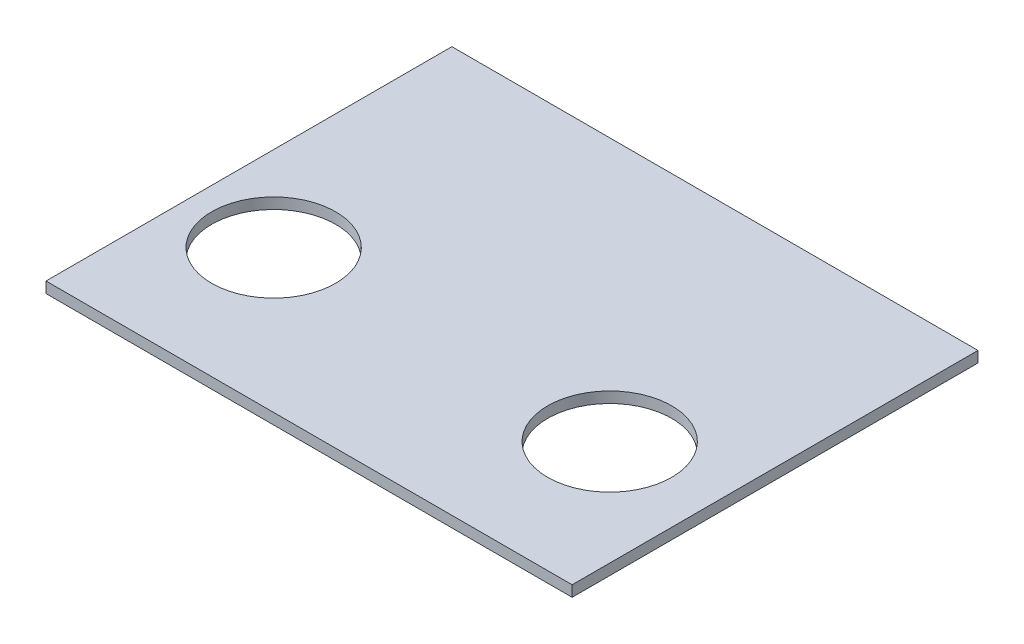
SolidWorks part; units mm, degrees
ref_plane "Plan de face" through (0, 0, 0) normal (0, 0, 1) x (1, 0, 0)
ref_plane "Plan de dessus" through (0, 0, 0) normal (0, 1, 0) x (1, 0, 0)
ref_plane "Plan de droite" through (0, 0, 0) normal (1, 0, 0) x (0, 0, -1)
sketch "Esquisse1" plane through (0, 0, 0) normal (0, 1, 0) x (1, 0, 0)
  line L1 (-35, 27) -> (35, 27)
  line L2 (-35, 27) -> (-35, -27)
  line L3 (-35, -27) -> (35, -27)
  line L4 (35, 27) -> (35, -27)
  line L5 (-35, 27) -> (35, -27) construction
  line L6 (-35, -27) -> (35, 27) construction
  point P0 (0, 0)
  dimension "D1" = 54
  dimension "D2" = 70
extrude "Boss.-Extru.1" add sketch "Esquisse1" along normal blind 1.45
sketch "Esquisse2" plane through (0, 1.45, 0) normal (0, 1, 0) x (1, 0, 0)
  line L0 (-35, -27) -> (35, -27) construction
  circle A0 centre (-23.7105, -8) radius 8.25
  dimension "D1" = 16.5
  dimension "D2" = 19
extrude "Enlèv. mat.-Extru.1" cut sketch "Esquisse2" against normal blind 10
sketch "Esquisse4" plane through (0, 1.45, 0) normal (0, 1, 0) x (1, 0, 0)
  line L0 (35, -27) -> (35, 27) construction
  line L1 (-35, -27) -> (35, -27) construction
  circle A0 centre (21, -8) radius 8.25
  dimension "D1" = 16.5
  dimension "D2" = 14
  dimension "D3" = 19
extrude "Enlèv. mat.-Extru.3" cut sketch "Esquisse4" against normal blind 10
